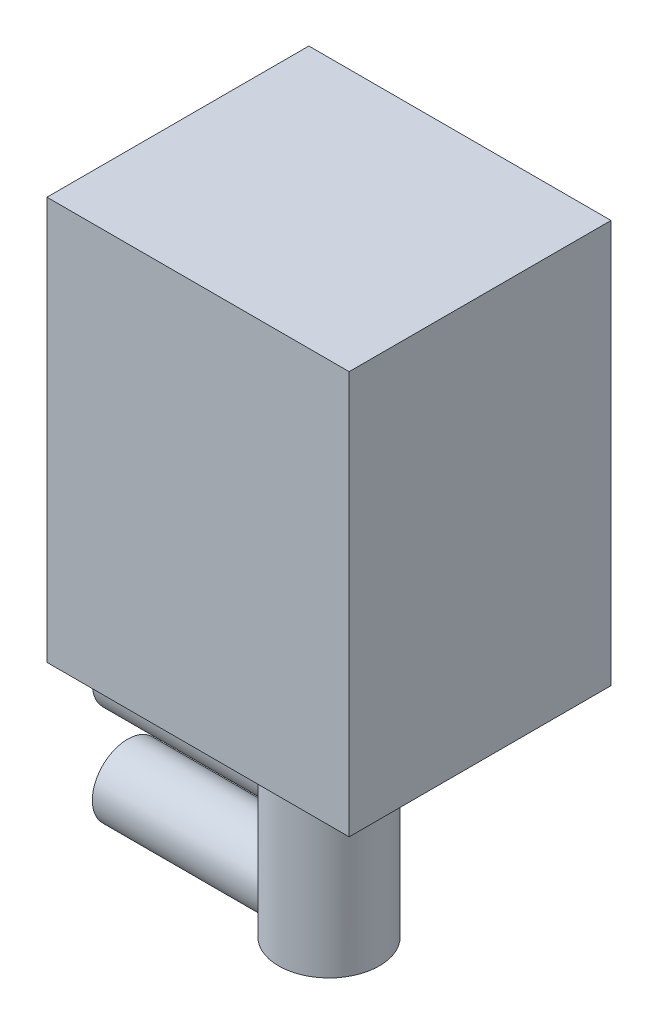
SolidWorks part; units mm, degrees
ref_plane "Front Plane" through (0, 0, 0) normal (1, 0, 0) x (0, 1, 0)
ref_plane "Top Plane" through (0, 0, 0) normal (0, 0, 1) x (0, 1, 0)
ref_plane "Right Plane" through (0, 0, 0) normal (0, 1, 0) x (-1, 0, 0)
sketch "Sketch1" plane through (0, 0, 0) normal (0, 0, 1) x (0, 1, 0)
  line L1 (0, 0) -> (-20, 0)
  line L2 (0, 0) -> (0, 15)
  line L3 (0, 15) -> (-20, 15)
  line L4 (-20, 0) -> (-20, 15)
  dimension "D1" = 20
  dimension "D2" = 15
extrude "Boss-Extrude1" add sketch "Sketch1" along normal blind 13
sketch "Sketch2" plane through (0, -20, 0) normal (0, -1, 0) x (1, 0, 0)
  line L1 (-15, 13) -> (-15, 0) construction
  line L2 (-15, 0) -> (0, 0) construction
  circle A0 centre (-7.5, 6.5) radius 2.5
  dimension "D1" = 5
  dimension "D2" = 7.5
  dimension "D3" = 6.5
extrude "Boss-Extrude2" add sketch "Sketch2" along normal blind 11.3
sketch "Sketch3" plane through (0, 0, 0) normal (1, 0, 0) x (0, 1, 0)
  line L0 (-31.3, 9) -> (-31.3, 4) construction
  line L1 (-31.3, 4) -> (-20, 4) construction
  circle A0 centre (-29.55, 6.5) radius 1.75
  circle A1 centre (-24.55, 6.5) radius 1.75
  dimension "D1" = 3.5
  dimension "D2" = 5
  dimension "D3" = 2.5
extrude "Boss-Extrude3" add sketch "Sketch3" against normal blind 10 from offset 7.5 offset against normal yes
